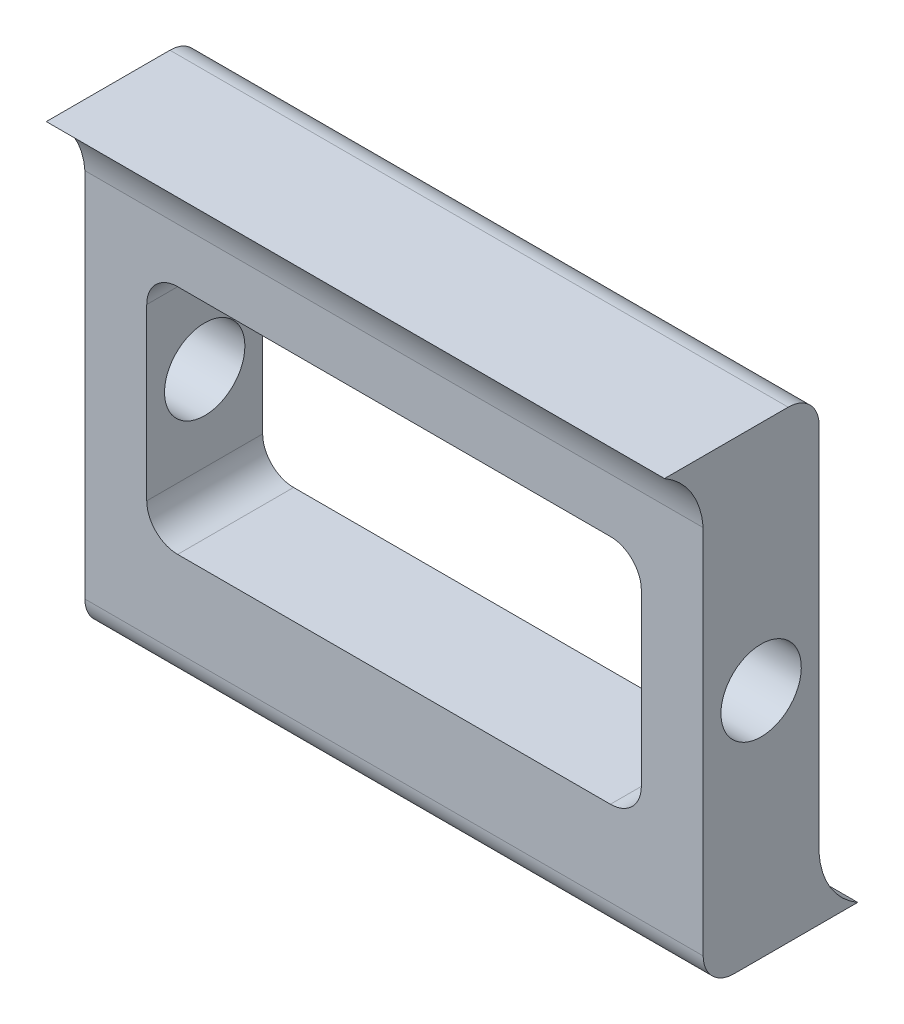
SolidWorks part; units mm, degrees
material "AISI 1020"
ref_plane "Front Plane" through (0, 0, 0) normal (0, 0, 1) x (1, 0, 0)
ref_plane "Top Plane" through (0, 0, 0) normal (0, 1, 0) x (1, 0, 0)
ref_plane "Right Plane" through (0, 0, 0) normal (1, 0, 0) x (0, 0, -1)
sketch "Sketch1" plane through (0, 0, 0) normal (0, 0, 1) x (1, 0, 0)
  line L1 (0, 0) -> (101.6, 0)
  line L2 (0, 0) -> (0, 76.2)
  line L3 (0, 76.2) -> (101.6, 76.2)
  line L4 (101.6, 0) -> (101.6, 76.2)
  dimension "D1" = 76.2
  dimension "D2" = 101.6
extrude "Boss-Extrude1" add sketch "Sketch1" along normal blind 19.05
sketch "Sketch3" plane through (0, 0, 19.05) normal (0, 0, 1) x (1, 0, 0)
  line L0 (10.16, 57.15) -> (91.44, 57.15)
  line L1 (91.44, 57.15) -> (91.44, 19.05)
  line L2 (91.44, 19.05) -> (10.16, 19.05)
  line L3 (10.16, 19.05) -> (10.16, 57.15)
  line L4 (101.6, 76.2) -> (0, 76.2) construction
  line L5 (101.6, 0) -> (101.6, 76.2) construction
  line L6 (0, 0) -> (101.6, 0) construction
  line L7 (0, 76.2) -> (0, 0) construction
  dimension "D1" = 19.05
  dimension "D2" = 10.16
  dimension "D3" = 19.05
  dimension "D4" = 10.16
extrude "Cut-Extrude1" cut sketch "Sketch3" against normal blind 25.4
sketch "Sketch4" plane through (101.6, 0, 0) normal (1, 0, 0) x (0, 0, -1)
  line L0 (-19.05, 76.2) -> (-25.4, 76.2)
  line L1 (-19.05, 0) -> (-19.05, 76.2) construction
  line L2 (0, 0) -> (6.35, 0)
  line L3 (-19.05, 66.04) -> (-19.05, 76.2)
  line L6 (0, 0) -> (0, 10.16)
  line L12 (0, 0) -> (0, 76.2) construction
  arc A0 (-25.4, 76.2) -> (-19.05, 66.04) centre (-31.7212, 65.1849) cw
  arc A3 (6.35, 0) -> (0, 10.16) centre (12.6712, 11.0151) cw
  dimension "D2" = 12.7
  dimension "D6" = 12.7
  dimension "D1" = 6.35
  dimension "D3" = 10.16
  dimension "D4" = 10.16
  dimension "D5" = 6.35
extrude "Boss-Extrude2" add sketch "Sketch4" against normal up to surface (101.6 mm away) up to face at (0, 38.1, 9.525)
sketch "Sketch5" plane through (101.6, 0, 0) normal (1, 0, 0) x (0, 0, -1)
  line L0 (-19.05, 0) -> (-19.05, 66.04) construction
  line L2 (-25.4, 76.2) -> (0, 76.2) construction
  circle A0 centre (-9.525, 38.1) radius 6.604
  dimension "D1" = 13.208
  dimension "D2" = 9.525
  dimension "D3" = 38.1
extrude "Cut-Extrude2" cut sketch "Sketch5" against normal up to surface (101.6 mm away) up to face at (0, 38.1, 9.525)
fillet "Fillet1" radius 5.08 6 edges at (50.8, 0, 19.05) (91.44, 19.05, 9.525) (10.16, 19.05, 9.525) (91.44, 57.15, 9.525) (10.16, 57.15, 9.525) (50.8, 76.2, 0)
